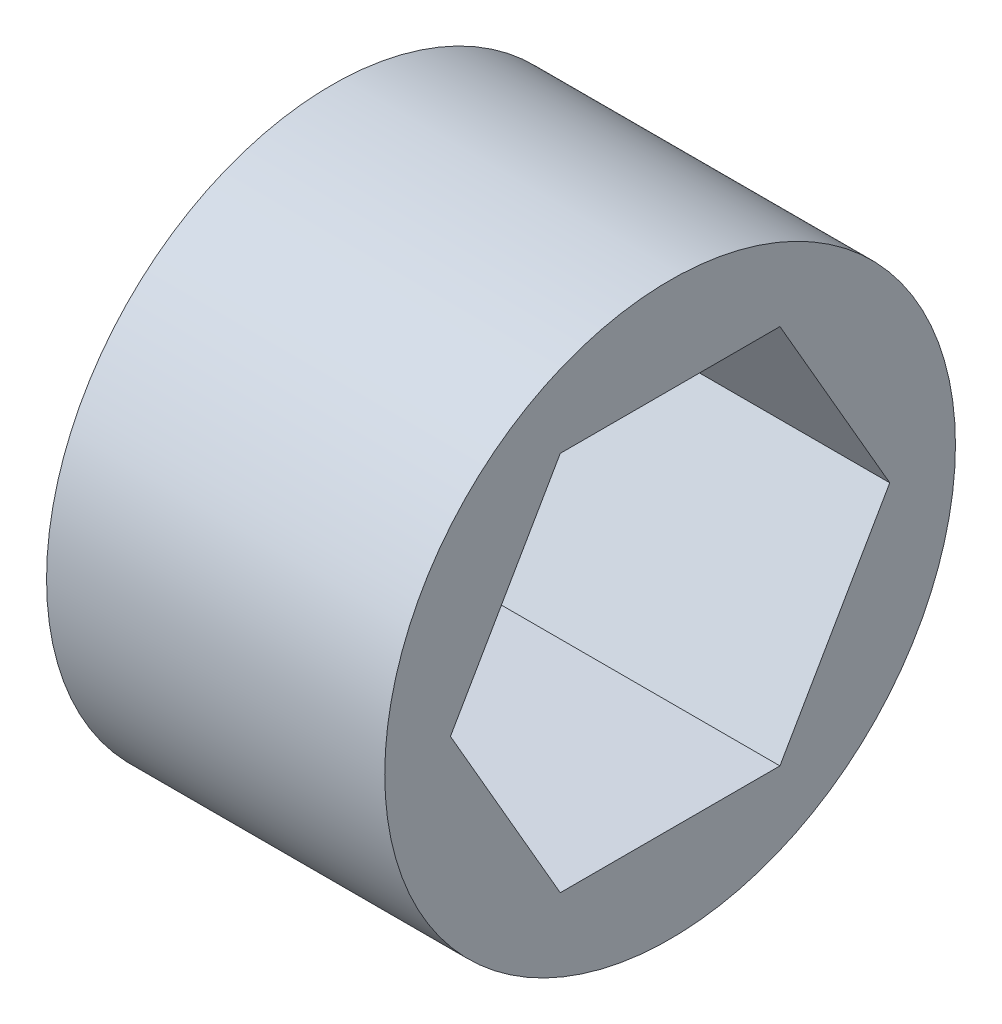
SolidWorks part; units mm, degrees
material "PET"
ref_plane "Front" through (0, 0, 0) normal (0, 0, 1) x (1, 0, 0)
ref_plane "Top" through (0, 0, 0) normal (0, 1, 0) x (1, 0, 0)
ref_plane "Right" through (0, 0, 0) normal (1, 0, 0) x (0, 0, -1)
sketch "Sketch1" plane through (0, 0, 0) normal (1, 0, 0) x (0, 0, -1)
  line L1 (7.3323, 0) -> (3.6662, 6.35)
  line L2 (3.6662, 6.35) -> (-3.6662, 6.35)
  line L3 (-3.6662, 6.35) -> (-7.3323, 0)
  line L4 (-7.3323, 0) -> (-3.6662, -6.35)
  line L5 (-3.6662, -6.35) -> (3.6662, -6.35)
  line L6 (3.6662, -6.35) -> (7.3323, 0)
  circle A0 centre (0, 0) radius 6.35 construction
  circle A1 centre (0, 0) radius 9.525
  dimension "D2" = 19.05
  dimension "D1" = 12.7
extrude "Boss-Extrude1" add sketch "Sketch1" along normal blind 11.2889
